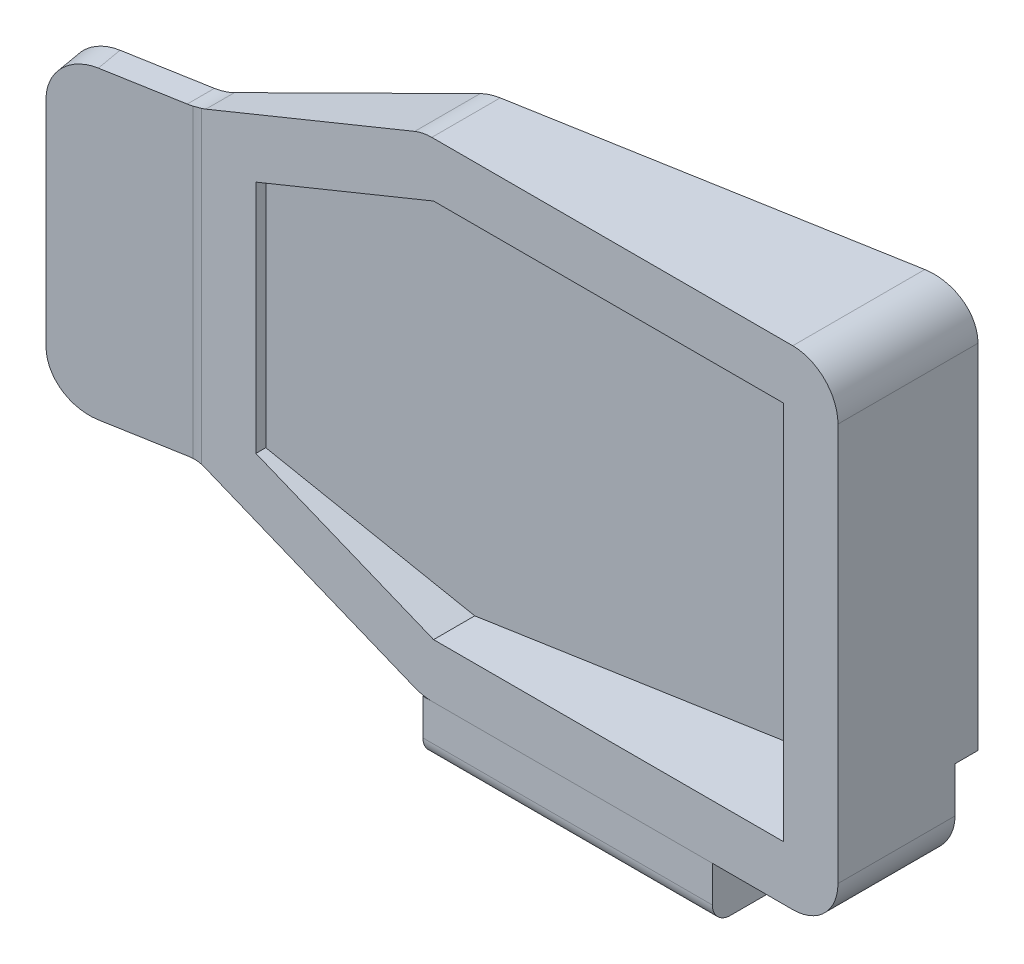
SolidWorks part; units mm, degrees
ref_plane "前视基准面" through (0, 0, 0) normal (0, 0, 1) x (1, 0, 0)
ref_plane "上视基准面" through (0, 0, 0) normal (0, 1, 0) x (1, 0, 0)
ref_plane "右视基准面" through (0, 0, 0) normal (1, 0, 0) x (0, 0, -1)
sketch "草图3" plane through (0, 0, 0) normal (0, 0, 1) x (1, 0, 0)
  line L0 (0, 25) -> (-43.5, 25) construction
  line L1 (-43.5, 25) -> (-66.8, 15.5) construction
  line L2 (-66.8, 15.5) -> (-66.8, -15.5) construction
  line L3 (-60.3864, 0) -> (-1.6213, 0) construction
  line L4 (0, 25) -> (0, -25) construction
  line L5 (-43.5, -25) -> (-66.8, -15.5) construction
  line L6 (0, -25) -> (-43.5, -25) construction
  line L7 (2, 27) -> (-43.8921, 27)
  line L8 (-43.8921, 27) -> (-68.8, 16.8444)
  line L9 (-68.8, 16.8444) -> (-68.8, -16.8444)
  line L10 (-43.8921, -27) -> (-68.8, -16.8444)
  line L11 (2, -27) -> (-43.8921, -27)
  line L12 (2, 27) -> (2, -27)
  point P10 (0, 0)
  dimension "D1" = 50
  dimension "D2" = 66.8
  dimension "D3" = 43.5
  dimension "D4" = 31
  dimension "D5" = 2
extrude "凸台-拉伸1" add sketch "草图3" along normal blind 20
sketch "草图5" plane through (0, 0, 20) normal (0, 0, 1) x (1, 0, 0)
  line L1 (-43.8921, -27) -> (-11.8921, -27)
  line L2 (-43.8921, -27) -> (-43.8921, -33)
  line L3 (-43.8921, -33) -> (-11.8921, -33)
  line L4 (-11.8921, -27) -> (-11.8921, -33)
  dimension "D1" = 32
  dimension "D2" = 6
extrude "凸台-拉伸3" add sketch "草图5" against normal blind 3 separate body
sketch "草图6" plane through (0, -33, 0) normal (0, -1, 0) x (-1, 0, 0)
  line L0 (11.8921, -17) -> (11.8921, -20) construction
  line L1 (43.8921, -20) -> (11.8921, -20)
  line L2 (43.8921, -20) -> (43.8921, -9)
  line L3 (43.8921, -9) -> (11.8921, -9)
  line L4 (11.8921, -20) -> (11.8921, -9)
  line L5 (27.8921, -17.2925) -> (27.8921, 4.2914) construction
  circle A0 centre (18.8921, -14) radius 1.2
  circle A1 centre (36.8921, -14) radius 1.2
  point P13 (27.8921, -20)
  dimension "D2" = 6
  dimension "D3" = 18
  dimension "D4" = 2.4
  dimension "D1" = 11
extrude "凸台-拉伸4" add sketch "草图6" against normal blind 3
sketch "草图8" plane through (0, 27, 0) normal (0, 1, 0) x (1, 0, 0)
  line L8 (-33.7058, 15.7528) -> (-33.7058, -19.7162) construction
  line L9 (-73.49, -20) -> (-68.8, -20)
  line L10 (-73.49, 2.6325) -> (-73.49, -20)
  line L11 (7.0981, 2.6325) -> (-73.49, 2.6325)
  line L12 (7.5298, -3.541) -> (7.0981, 2.6325)
  line L13 (-68.8, -17) -> (7.5298, -3.541)
  line L14 (-68.8, -20) -> (-68.8, -17)
  line L15 (-68.8, -20) -> (-68.8, 0) construction
  line L16 (-43.8921, -20) -> (-68.8, -20) construction
  dimension "D1" = 10
  dimension "D2" = 3
extrude "切除-拉伸2" cut sketch "草图8" against normal blind 80
sketch "草图9" plane through (0.8326, 0, 4.7219) normal (-0.1736, 0, -0.9848) x (-0.9848, 0, 0.1736)
  line L1 (70.7068, 16.8444) -> (85.7068, 16.8444)
  line L2 (70.7068, 16.8444) -> (70.7068, -16.8444)
  line L3 (70.7068, -16.8444) -> (85.7068, -16.8444)
  line L4 (85.7068, 16.8444) -> (85.7068, -16.8444)
  dimension "D1" = 15
extrude "凸台-拉伸6" add sketch "草图9" against normal up to vertex (2.9544 mm away) up to point (-68.8, 16.8444, 20)
fillet "圆角1" radius 5 9 edges at (2, 27, 12.258) (2, -27, 12.258) (-68.8, -16.8444, 18.5) (-68.8, 16.8444, 18.5) (-43.8921, -27, 16.304) (-83.3156, -16.8444, 21.0595) (-83.3156, 16.8444, 21.0595) (-43.8921, 27, 16.304) (-68.8, 0, 20)
ref_plane "基准面5" through (1.3535, 0, 7.6763) normal (-0.1736, 0, -0.9848) x (-0.9848, 0, 0.1736)
sketch "草图10" plane through (0, 0, 20) normal (0, 0, 1) x (1, 0, 0)
  line L0 (-4, -21) -> (-4, 21)
  line L1 (-4, 21) -> (-42.7159, 21)
  line L2 (-42.7159, 21) -> (-62.3626, 12.9896)
  line L3 (-62.3626, 12.9896) -> (-62.3626, -12.9896)
  line L4 (-62.3626, -12.9896) -> (-42.7159, -21)
  line L5 (-42.7159, -21) -> (-4, -21)
  line L6 (2, -22) -> (2, 22)
  line L7 (-3, 27) -> (-42.9119, 27)
  line L8 (-44.7997, 26.6299) -> (-67.8924, 17.2145)
  line L9 (-68.3626, 17.0496) -> (-68.3626, -17.0496)
  line L10 (-67.8924, -17.2145) -> (-44.7997, -26.6299)
  line L11 (-42.9119, -27) -> (-3, -27)
  line L12 (2, -22) -> (2, 22) construction
  line L13 (-3, 27) -> (-42.9119, 27) construction
  line L14 (-44.7997, 26.6299) -> (-67.8924, 17.2145) construction
  line L15 (-68.3626, 17.0496) -> (-68.3626, -17.0496) construction
  line L16 (-67.8924, -17.2145) -> (-44.7997, -26.6299) construction
  line L17 (-42.9119, -27) -> (-3, -27) construction
  arc A0 (-4, 21) -> (-4, 21) centre (-4, 21) ccw
  arc A1 (-42.7159, 21) -> (-42.7159, 21) centre (-42.7159, 21) ccw
  arc A2 (-62.3626, 12.9896) -> (-62.3626, 12.9896) centre (-62.3626, 12.9896) cw
  arc A3 (-62.3626, -12.9896) -> (-62.3626, -12.9896) centre (-62.3626, -12.9896) cw
  arc A4 (-42.7159, -21) -> (-42.7159, -21) centre (-42.7159, -21) ccw
  arc A5 (-4, -21) -> (-4, -21) centre (-4, -21) ccw
  arc A6 (2, 22) -> (-3, 27) centre (-3, 22) ccw
  arc A7 (-42.9119, 27) -> (-44.7997, 26.6299) centre (-42.9119, 22) ccw
  arc A8 (-68.3626, 17.0496) -> (-67.8924, 17.2145) centre (-69.7801, 21.8444) ccw
  arc A9 (-67.8924, -17.2145) -> (-68.3626, -17.0496) centre (-69.7801, -21.8444) ccw
  arc A10 (-44.7997, -26.6299) -> (-42.9119, -27) centre (-42.9119, -22) ccw
  arc A11 (-3, -27) -> (2, -22) centre (-3, -22) ccw
  arc A12 (2, 22) -> (-3, 27) centre (-3, 22) ccw construction
  arc A13 (-42.9119, 27) -> (-44.7997, 26.6299) centre (-42.9119, 22) ccw construction
  arc A14 (-68.3626, 17.0496) -> (-67.8924, 17.2145) centre (-69.7801, 21.8444) ccw construction
  arc A15 (-67.8924, -17.2145) -> (-68.3626, -17.0496) centre (-69.7801, -21.8444) ccw construction
  arc A16 (-44.7997, -26.6299) -> (-42.9119, -27) centre (-42.9119, -22) ccw construction
  arc A17 (-3, -27) -> (2, -22) centre (-3, -22) ccw construction
  dimension "D1" = 0
  dimension "D2" = 6
extrude "切除-拉伸3" cut sketch "草图10" against normal up to surface (1.0888 mm away) up to plane "基准面5"
sketch "草图11" plane through (0, -30, 0) normal (0, 1, 0) x (1, 0, 0)
  line L0 (-45.4501, -12.8828) -> (-20.4375, -8.4724)
  line L1 (-44.7997, -12.7681) -> (-67.8924, -16.84) construction
  line L2 (-42.9119, -12.4352) -> (-3, -5.3977) construction
  line L3 (-20.4375, -8.4724) -> (-47.341, -4.3212)
  line L4 (-47.341, -4.3212) -> (-45.4501, -12.8828)
extrude "切除-拉伸4" cut sketch "草图11" against normal up to surface (3 mm away) up to face at (-27.8921, -33, 14.5)
sketch "草图12" plane through (0.8326, 0, 4.7219) normal (-0.1736, 0, -0.9848) x (-0.9848, 0, 0.1736)
  line L0 (-1.1854, -17) -> (86.4558, -17)
  line L1 (-1.1854, -22) -> (-1.1854, 22) construction
  line L2 (86.4558, -17) -> (86.4558, -28.0091)
  line L3 (86.4558, -28.0091) -> (-1.1854, -28.0091)
  line L4 (-1.1854, -28.0091) -> (-1.1854, -17)
  line L5 (44.4193, -27) -> (3.8917, -27) construction
  dimension "D1" = 10
extrude "切除-拉伸5" cut sketch "草图12" against normal blind 2.5
fillet "圆角2" radius 2 2 edges at (-27.8921, -30, 17) (-27.8921, -33, 20)
